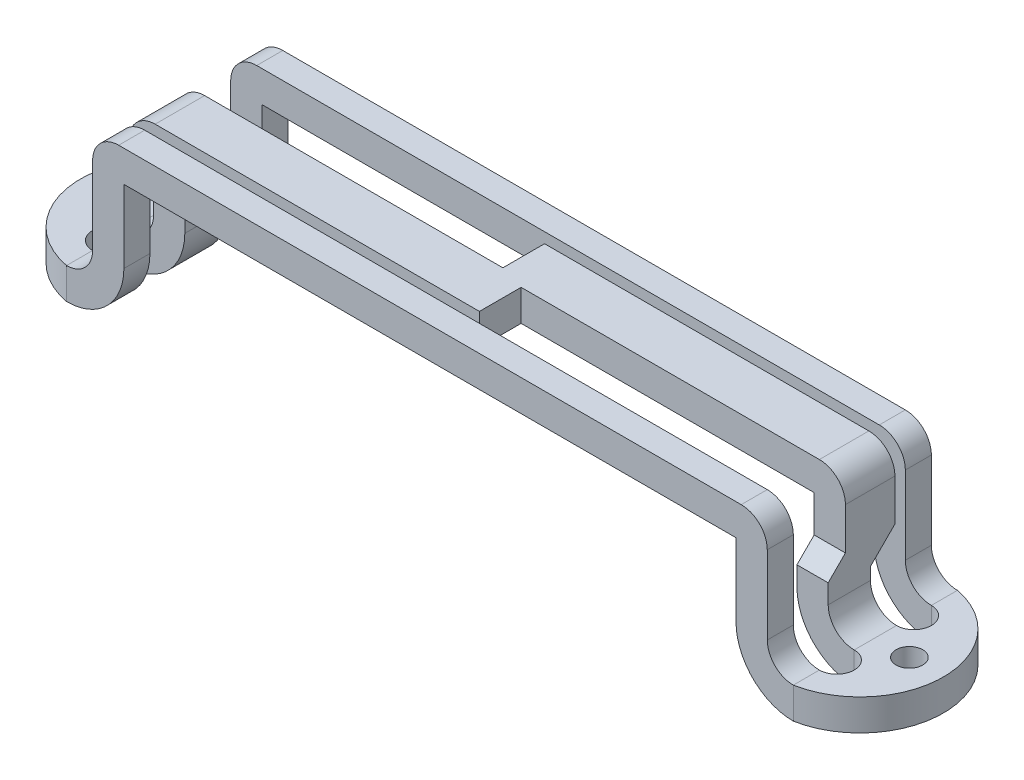
SolidWorks part; units mm, degrees
material "6061-T6 (SS)"
ref_plane "Front Plane" through (0, 0, 0) normal (0, 0, 1) x (1, 0, 0)
ref_plane "Top Plane" through (0, 0, 0) normal (0, 1, 0) x (1, 0, 0)
ref_plane "Right Plane" through (0, 0, 0) normal (1, 0, 0) x (0, 0, -1)
sketch "Sketch1" plane through (0, 0, 0) normal (0, 0, 1) x (1, 0, 0)
  line L0 (-30.353, 0) -> (30.353, 0)
  line L1 (-32.893, -2.54) -> (-32.893, -10.16)
  line L2 (-35.433, -12.7) -> (-42.0688, -12.7)
  line L3 (0, 0) -> (0, -13.9437) construction
  line L4 (35.433, -12.7) -> (42.0688, -12.7)
  line L5 (32.893, -2.54) -> (32.893, -10.16)
  arc A0 (35.433, -12.7) -> (32.893, -10.16) centre (35.433, -10.16) cw
  arc A1 (30.353, 0) -> (32.893, -2.54) centre (30.353, -2.54) cw
  arc A2 (-30.353, 0) -> (-32.893, -2.54) centre (-30.353, -2.54) ccw
  arc A3 (-32.893, -10.16) -> (-35.433, -12.7) centre (-35.433, -10.16) cw
  point P2 (0, 0)
  point P12 (32.893, -12.7)
  point P15 (32.893, 0)
  point P18 (-32.893, 0)
  point P21 (-32.893, -12.7)
  dimension "D4" = 2.54
  dimension "D1" = 84.1375
  dimension "D2" = 65.786
  dimension "D3" = 12.7
extrude "Extrude-Thin1" add sketch "Sketch1" against normal blind 16.002 thin thin type one direction wall 3.048
sketch "Sketch2" plane through (0, 0, 0) normal (0, 1, 0) x (1, 0, 0)
  line L0 (-35.433, 16.002) -> (-42.0688, 16.002)
  line L1 (-42.0688, 16.002) -> (-42.0688, 0)
  line L2 (-42.0688, 0) -> (-35.433, 0)
  line L3 (35.433, 0) -> (42.0688, 0)
  line L4 (42.0688, 0) -> (42.0688, 16.002)
  line L5 (42.0688, 16.002) -> (35.433, 16.002)
  line L6 (-42.0688, 8.001) -> (-35.433, 8.001) construction
  line L7 (-35.433, 16.002) -> (-35.433, 0) construction
  line L8 (-35.433, 8.001) -> (35.433, 8.001) construction
  line L9 (35.433, 16.002) -> (35.433, 0) construction
  line L10 (35.433, 8.001) -> (42.0688, 8.001) construction
  line L11 (-35.433, 16.002) -> (-35.433, 13.462) construction
  line L12 (-35.433, 13.462) -> (-1.27, 13.462)
  line L13 (-1.27, 13.462) -> (0, 13.462)
  line L14 (0, 0) -> (0, 16.002) construction
  line L15 (-30.353, 16.002) -> (30.353, 16.002) construction
  line L16 (0, 13.462) -> (35.433, 13.462)
  line L18 (-32.893, 8.382) -> (-1.27, 8.382)
  line L19 (-1.27, 8.382) -> (-1.27, 12.446)
  line L20 (-35.433, 2.54) -> (-35.433, 4.24) construction
  line L21 (-35.433, 13.462) -> (-35.433, 11.762) construction
  line L22 (-35.433, 10.062) -> (-32.893, 10.062)
  line L23 (-32.893, 16.002) -> (-32.893, 0) construction
  line L24 (-32.893, 10.062) -> (-32.893, 8.382)
  line L25 (-35.433, 5.94) -> (-32.893, 5.94)
  line L26 (0, 2.54) -> (-35.433, 2.54)
  line L27 (-32.893, 3.556) -> (1.27, 3.556)
  line L28 (1.27, 2.54) -> (0, 2.54)
  line L29 (1.27, 7.62) -> (1.27, 3.556)
  line L30 (35.433, 2.54) -> (1.27, 2.54)
  line L31 (32.893, 7.62) -> (1.27, 7.62)
  line L32 (35.433, 13.462) -> (35.433, 11.762) construction
  line L33 (35.433, 2.54) -> (35.433, 4.24) construction
  line L34 (35.433, 10.062) -> (32.893, 10.062)
  line L35 (32.893, 16.002) -> (32.893, 0) construction
  line L36 (32.893, 10.062) -> (32.893, 12.446)
  line L37 (35.433, 5.94) -> (32.893, 5.94)
  line L38 (32.893, 5.94) -> (32.893, 7.62)
  line L39 (-32.893, 5.94) -> (-32.893, 3.556)
  line L40 (32.893, 12.446) -> (-1.27, 12.446)
  arc A0 (-35.433, 16.002) -> (-35.433, 0) centre (-33.9273, 8.001) ccw
  arc A1 (35.433, 16.002) -> (35.433, 0) centre (33.9273, 8.001) cw
  circle A2 centre (-38.7509, 8.001) radius 1.3
  circle A3 centre (38.7509, 8.001) radius 1.3
  arc A6 (-35.433, 5.94) -> (-35.433, 2.54) centre (-35.433, 4.24) ccw
  arc A7 (-35.433, 13.462) -> (-35.433, 10.062) centre (-35.433, 11.762) ccw
  arc A10 (35.433, 10.062) -> (35.433, 13.462) centre (35.433, 11.762) ccw
  arc A11 (35.433, 2.54) -> (35.433, 5.94) centre (35.433, 4.24) ccw
  line M4 (30.353, 0) -> (30.353, 16.002)
  line M6 (-30.353, 16.002) -> (-30.353, 0)
  dimension "D4" = 2.6
  dimension "D1" = 2.54
  dimension "D2" = 1.27
  dimension "D3" = 5.08
extrude "Cut-Extrude1" cut sketch "Sketch2" against normal through all contours A0 L0 L1 | A0 L1 L2 | L18 L12 M6 | L18 L19 L16 L13 L12 M4 M6 | L31 L29 L27 L26 L28 L30 M4 M6 | L31 L30 M4 | A3 | L4 A1 L3 | L5 A1 L4 | L16 M4 | L26 L27 M6 | A2 | L19 L40 L36 L34 A10 L16 L13 L12 A7 L22 L24 L18 region at (-40.3835, 0, -14.1912) region at (-40.3835, 0, -1.8108) region at (40.3835, 0, -1.8108) region at (40.3835, 0, -14.1912) region at (-33.2529, 0, -11.3464) region at (-10.3898, 0, -11.285) region at (-34.3208, 0, -4.0448) region at (10.3898, 0, -4.717) region at (34.3208, 0, -11.9572) region at (33.2529, 0, -4.6556) region at (-38.7509, 0, -8.001) region at (38.7509, 0, -8.001)
sketch "Sketch3" plane through (0, 0, 0) normal (0, 1, 0) x (1, 0, 0)
  line L0 (-32.893, 13.462) -> (-30.353, 13.462) construction
  line L1 (-1.27, 8.382) -> (-31.623, 8.382)
  line L2 (-1.27, 8.382) -> (-1.27, 13.462)
  line L3 (-1.27, 13.462) -> (-31.623, 13.462)
  line L4 (-31.623, 8.382) -> (-31.623, 13.462)
  line L6 (1.27, 7.62) -> (31.623, 7.62)
  line L7 (1.27, 7.62) -> (1.27, 2.54)
  line L8 (1.27, 2.54) -> (31.623, 2.54)
  line L9 (31.623, 7.62) -> (31.623, 2.54)
  line L10 (32.893, 2.54) -> (30.353, 2.54) construction
extrude "Boss-Extrude1" [suppressed] add sketch "Sketch3" against normal blind 2.54 separate body
sketch "Sketch4" plane through (0, 0, 0) normal (0, 1, 0) x (1, 0, 0)
  line L0 (0, 0) -> (0, 16.002) construction
  line L1 (-30.353, 16.002) -> (30.353, 16.002) construction
  line L21 (-32.893, 17.272) -> (-35.5471, 17.272)
  line L22 (-35.5471, -1.27) -> (-32.893, -1.27)
  line L23 (-32.893, -1.27) -> (-30.353, -1.27)
  line L24 (-30.353, -1.27) -> (30.353, -1.27)
  line L25 (30.353, -1.27) -> (32.893, -1.27)
  line L26 (32.893, -1.27) -> (35.5471, -1.27)
  line L27 (35.5471, 17.272) -> (32.893, 17.272)
  line L28 (32.893, 17.272) -> (30.353, 17.272)
  line L29 (-30.353, 17.272) -> (30.353, 17.272)
  line L30 (-30.353, 17.272) -> (-32.893, 17.272)
  line L32 (-43.3388, 8.001) -> (43.3388, 8.001) construction
  arc A4 (-35.5471, 17.272) -> (-35.5471, -1.27) centre (-33.9273, 8.001) ccw
  arc A5 (35.5471, -1.27) -> (35.5471, 17.272) centre (33.9273, 8.001) ccw
sketch "Sketch6" plane through (0, 0, -8.382) normal (0, 0, -1) x (-1, 0, 0)
  line L0 (32.893, -10.16) -> (32.893, -2.54) construction
  line L1 (32.893, -15.1374) -> (32.893, -10.16) construction
  line L2 (29.845, -3.048) -> (29.845, -10.16) construction
  line L3 (32.893, -10.16) -> (32.893, -6.604)
  line L4 (32.893, -15.1374) -> (32.893, -10.16)
  line L5 (29.845, -6.604) -> (29.845, -10.16)
  line L7 (32.893, -10.16) -> (32.893, -6.604) construction
  line L8 (32.893, -6.604) -> (29.845, -6.604)
  arc A0 (29.845, -10.16) -> (32.893, -15.1374) centre (35.433, -10.16) ccw construction
  arc A1 (29.845, -10.16) -> (32.893, -15.1374) centre (35.433, -10.16) ccw
extrude "Boss-Extrude2" add sketch "Sketch6" along normal up to surface (1.68 mm away) up to face at (-34.0224, -13.6055, -10.062)
sketch "Sketch7" plane through (0, 0, -7.62) normal (0, 0, 1) x (1, 0, 0)
  line L0 (32.893, -10.16) -> (32.893, -2.54) construction
  line L1 (32.893, -15.1374) -> (32.893, -10.16) construction
  line L2 (29.845, -3.048) -> (29.845, -10.16) construction
  line L3 (32.893, -10.16) -> (32.893, -6.6)
  line L4 (32.893, -15.1374) -> (32.893, -10.16)
  line L5 (29.845, -6.604) -> (29.845, -10.16)
  line L6 (32.893, -10.16) -> (32.893, -6.6) construction
  line L7 (32.893, -6.6) -> (29.845, -6.604)
  arc A0 (29.845, -10.16) -> (32.893, -15.1374) centre (35.433, -10.16) ccw construction
  arc A1 (29.845, -10.16) -> (32.893, -15.1374) centre (35.433, -10.16) ccw
extrude "Boss-Extrude3" add sketch "Sketch7" along normal up to surface (1.68 mm away) up to face at (34.0224, -13.6055, -5.94)
sketch "Sketch8" plane through (0, 0, -12.446) normal (0, 0, -1) x (-1, 0, 0)
  line L0 (-32.893, -15.1374) -> (-32.893, -2.54) construction
  line L1 (-29.845, -3.048) -> (-29.845, -10.16) construction
  line L2 (-32.893, -15.1374) -> (-32.893, -6.6)
  line L3 (-29.845, -6.604) -> (-29.845, -10.16)
  line L4 (-29.845, -6.604) -> (-32.893, -6.6)
  arc A0 (-32.893, -15.1374) -> (-29.845, -10.16) centre (-35.433, -10.16) ccw construction
  arc A1 (-32.893, -15.1374) -> (-29.845, -10.16) centre (-35.433, -10.16) ccw
extrude "Cut-Extrude2" cut sketch "Sketch8" against normal up to surface (2.384 mm away) up to face at (34.0224, -13.6055, -10.062)
sketch "Sketch9" plane through (0, 0, -3.556) normal (0, 0, 1) x (1, 0, 0)
  line L0 (-32.893, -15.1374) -> (-32.893, -2.54) construction
  line L1 (-29.845, -3.048) -> (-29.845, -10.16) construction
  line L2 (-32.893, -15.1374) -> (-32.893, -6.604)
  line L3 (-29.845, -6.604) -> (-29.845, -10.16)
  line L4 (-32.893, -6.604) -> (-29.845, -6.604)
  arc A0 (-32.893, -15.1374) -> (-29.845, -10.16) centre (-35.433, -10.16) ccw construction
  arc A1 (-32.893, -15.1374) -> (-29.845, -10.16) centre (-35.433, -10.16) ccw
extrude "Cut-Extrude3" cut sketch "Sketch9" against normal up to surface (2.384 mm away) up to face at (-34.0224, -13.6055, -5.94)
chamfer "Chamfer1" distance 1.7 angle 45 2 edges at (-31.369, -6.604, -10.062) (31.369, -6.602, -5.94)
chamfer "Chamfer2" distance 2.38 angle 45 2 edges at (-31.369, -6.604, -5.94) (31.369, -6.602, -10.062)
sketch "Sketch10" plane through (0, -3.048, 0) normal (0, -1, 0) x (1, 0, 0)
  line L0 (-29.845, 0) -> (-29.845, -16.002) construction
  line L1 (-29.845, -1.251) -> (-29.845, -14.751)
  line L2 (-29.845, -1.251) -> (-12.845, -1.251)
  line L3 (-12.845, -1.251) -> (-12.845, -14.751)
  line L4 (-12.845, -14.751) -> (-29.845, -14.751)
  point P7 (-29.845, -8.001)
  dimension "D1" = 13.5
  dimension "D2" = 17
extrude "Boss-Extrude4" [suppressed] add sketch "Sketch10" along normal blind 12
sketch "Sketch11" [suppressed] plane through (-12.845, 0, 0) normal (1, 0, 0) x (0, 0, -1)
  line L0 (14.751, -15.048) -> (1.251, -3.048) construction
  circle A0 centre (8.001, -9.048) radius 5.6
  circle A1 centre (8.001, -9.048) radius 5
extrude "Boss-Extrude5" [suppressed] add sketch "Sketch11" along normal blind 15
fillet "Fillet1" [suppressed] radius 4
